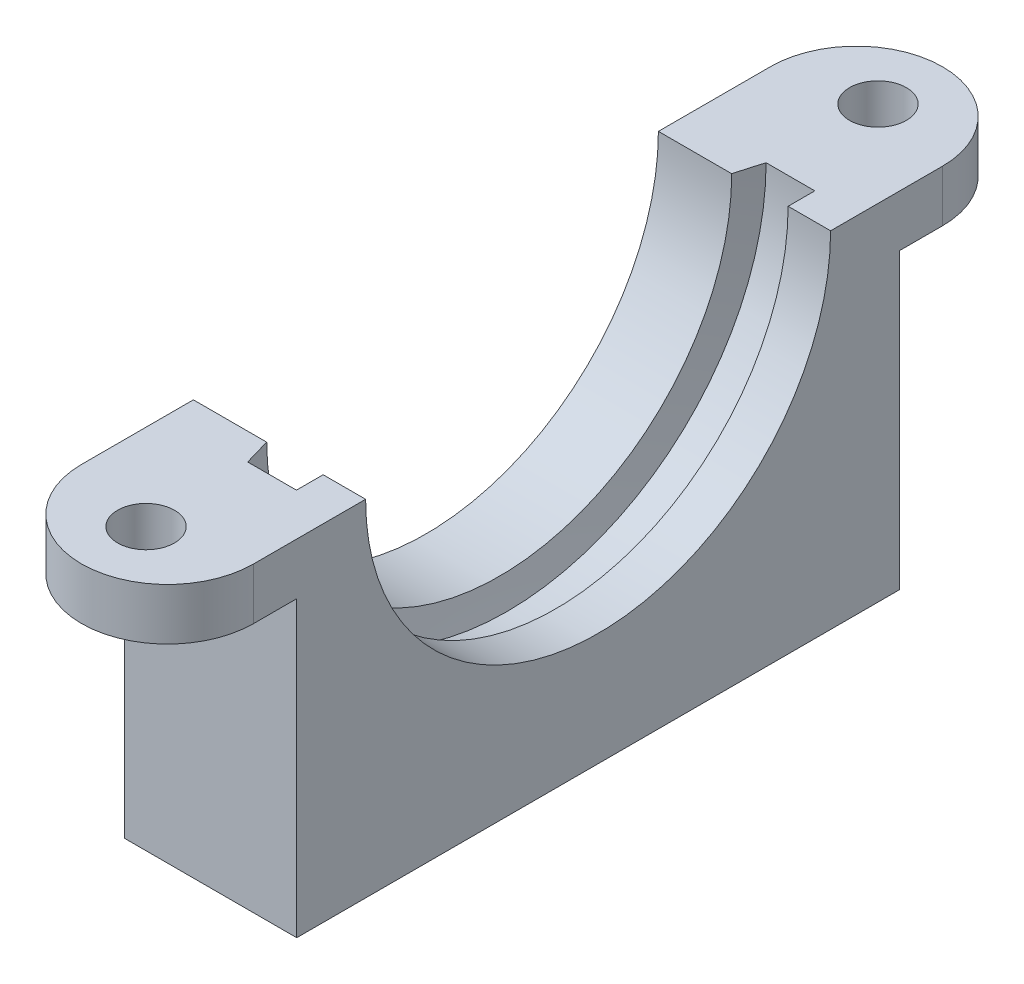
SolidWorks part; units mm, degrees
ref_plane "Front Plane" through (0, 0, 0) normal (0, 0, 1) x (1, 0, 0)
ref_plane "Top Plane" through (0, 0, 0) normal (0, 1, 0) x (1, 0, 0)
ref_plane "Right Plane" through (0, 0, 0) normal (1, 0, 0) x (0, 0, -1)
sketch "Sketch1" plane through (0, 0, 0) normal (0, 0, 1) x (1, 0, 0)
  line L1 (0, 15.05) -> (-2.83, 15.05)
  line L3 (0, 0) -> (-5.0677, 0)
  line L4 (0, 15.05) -> (0, 0)
  line L5 (-5.0677, 0) -> (-5.0677, 15.05) construction
  line L6 (-2.5338, 0) -> (-2.5338, -15.05) construction
  line L7 (-7.5338, 0) -> (2.4662, 0)
  line L8 (-7.5338, 0) -> (-7.5338, -20.05)
  line L9 (-7.5338, -20.05) -> (2.4662, -20.05)
  line L10 (2.4662, 0) -> (2.4662, -20.05)
  line L11 (-2.5338, -15.05) -> (-2.5338, -20.05) construction
  arc A0 (-5.0677, 0) -> (-2.83, 15.05) centre (46.6623, 0) cw
  point P4 (0, 0)
  dimension "D2" = 51.73
  dimension "D3" = 2.83
  dimension "D1" = 15.05
  dimension "D4" = 10
  dimension "D5" = 5
extrude "Boss-Extrude4" add sketch "Sketch1" along normal mid plane 35 contours L8 L9 L10 L7
revolve "Cut-Revolve4" cut sketch "Sketch1<5>" angle 360 about L3
sketch "Sketch1<5>" plane through (0, 0, 0) normal (0, 0, 1) x (1, 0, 0) same geometry as "Sketch1"
sketch "Sketch11" plane through (-7.5338, 0, 0) normal (-1, 0, 0) x (0, 0, 1)
  circle A0 centre (0, 0) radius 13.5
  arc A1 (-15.05, 0) -> (15.05, 0) centre (0, 0) ccw construction
  dimension "D1" = 27
extrude "Cut-Extrude5" cut sketch "Sketch11" against normal through all
sketch "Sketch13" plane through (0, 0, 0) normal (0, 1, 0) x (1, 0, 0)
  line L0 (-7.5338, -20) -> (2.4662, -20) construction
  line L1 (2.4662, 17.5) -> (-7.5338, 17.5)
  line L2 (2.4662, 17.5) -> (2.4662, 20)
  line L4 (-7.5338, 17.5) -> (-7.5338, 20)
  line L5 (2.4662, -17.5) -> (-7.5338, -17.5)
  line L6 (2.4662, -17.5) -> (2.4662, -20)
  line L8 (-7.5338, -17.5) -> (-7.5338, -20)
  line L9 (-7.5338, 20) -> (2.4662, 20) construction
  line L10 (-2.5338, -25) -> (-2.5338, -17.5) construction
  line L11 (-2.5338, 17.5) -> (-2.5338, 25) construction
  arc A0 (2.4662, -20) -> (-7.5338, -20) centre (-2.5338, -20) cw
  arc A1 (-7.5338, 20) -> (2.4662, 20) centre (-2.5338, 20) cw
  circle A2 centre (-2.5338, -21.25) radius 1.65
  circle A3 centre (-2.5338, 21.25) radius 1.65
  point P20 (-2.5338, -21.25)
  dimension "D2" = 3.3
  dimension "D1" = 2.5
extrude "Boss-Extrude7" add sketch "Sketch13" against normal blind 3
equation "\"D3@Sketch1\"=2.78+0.05"
equation "\"D1@Sketch1\"=15+0.05"
equation "\"D2@Sketch1\"=51.68+0.05"
